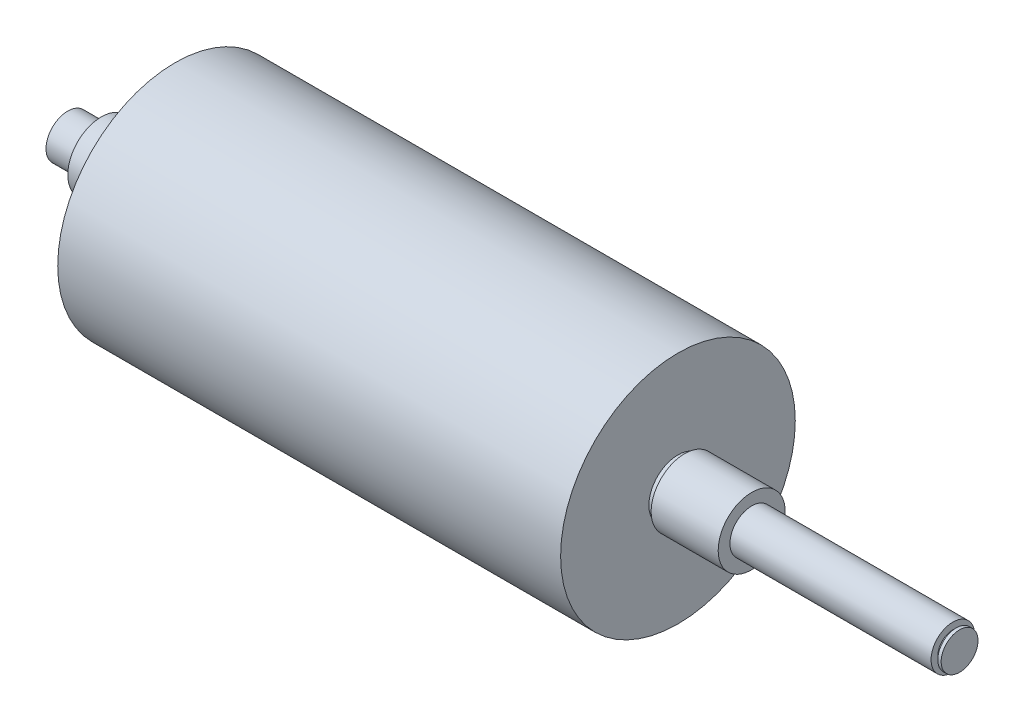
SolidWorks part; units mm, degrees
ref_plane "Plan de face" through (0, 0, 0) normal (0, 0, 1) x (1, 0, 0)
ref_plane "Plan de dessus" through (0, 0, 0) normal (0, 1, 0) x (1, 0, 0)
ref_plane "Plan de droite" through (0, 0, 0) normal (1, 0, 0) x (0, 0, -1)
sketch "Esquisse1" plane through (0, 0, 0) normal (0, 0, 1) x (1, 0, 0)
  line L0 (0, 0) -> (0, 100)
  line L1 (0, 100) -> (300, 100)
  line L2 (300, 100) -> (300, 74.3143)
  line L3 (300, 74.3143) -> (320, 74.3143)
  line L4 (320, 74.3143) -> (320, 350)
  line L5 (320, 350) -> (1820, 350)
  line L6 (1820, 350) -> (1820, 86.7213)
  line L7 (1820, 86.7213) -> (1840, 86.7213)
  line L8 (1840, 86.7213) -> (1840, 100)
  line L9 (1840, 100) -> (2140, 100)
  line L10 (2140, 100) -> (2140, 0)
  line L11 (2140, 0) -> (0, 0)
  dimension "D1" = 1500
  dimension "D2" = 300
  dimension "D3" = 20
  dimension "D4" = 20
  dimension "D5" = 300
  dimension "D6" = 350
  dimension "D7" = 100
  dimension "D8" = 100
revolve "Révolution1" add sketch "Esquisse1" angle 360 about L11 region at (1070.3206, 161.5132, 0)
sketch "Esquisse2" plane through (0, 0, 0) normal (-1, 0, 0) x (0, 0, 1)
  circle A0 centre (0, 0) radius 65
  circle A1 centre (0, 0) radius 100 construction
  circle A2 centre (0, 0) radius 100
  dimension "D1" = 130
extrude "Enlèv. mat.-Extru.1" cut sketch "Esquisse2" against normal blind 100
sketch "Esquisse3" plane through (2140, 0, 0) normal (1, 0, 0) x (0, 0, -1)
  circle A0 centre (0, 0) radius 65
  circle A1 centre (0, 0) radius 100 construction
  circle A2 centre (0, 0) radius 100
extrude "Enlèv. mat.-Extru.2" cut sketch "Esquisse3" against normal blind 100
sketch "Esquisse5" plane through (2140, 0, 0) normal (1, 0, 0) x (0, 0, -1)
  circle A1 centre (0, 0) radius 65
  circle A2 centre (0, 0) radius 65
  dimension "D1" = 0
extrude "Boss.-Extru.2" add sketch "Esquisse5" along normal blind 520
sketch "Esquisse6" plane through (2660, 0, 0) normal (1, 0, 0) x (0, 0, -1)
  circle A0 centre (0, 0) radius 65
  circle A1 centre (0, 0) radius 45
extrude "Enlèv. mat.-Extru.3" cut sketch "Esquisse6" against normal blind 20
sketch "Esquisse7" plane through (2660, 0, 0) normal (1, 0, 0) x (0, 0, -1)
  circle A0 centre (0, 0) radius 55
extrude "Boss.-Extru.3" add sketch "Esquisse7" against normal blind 10
sketch "Esquisse11" plane through (0, 563.2692, -380.9564) normal (0, 0.8283, -0.5602) x (1, 0, 0)
  circle A0 centre (1225, -300) radius 326.3228
